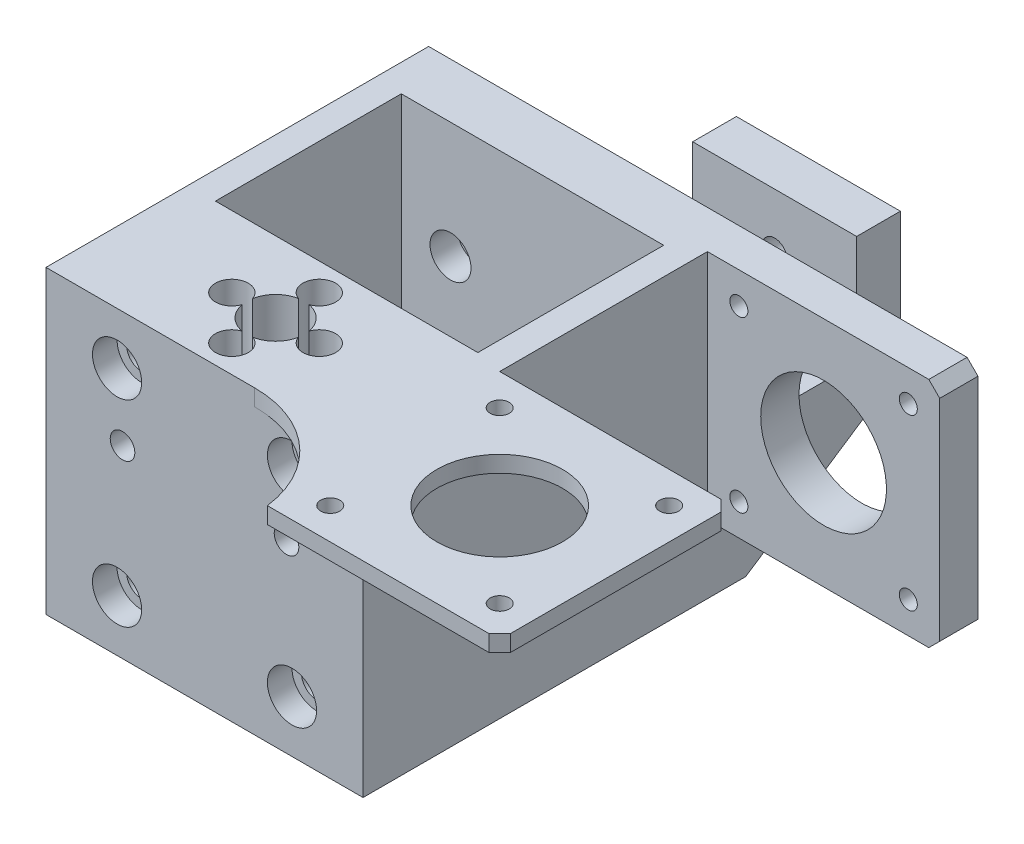
SolidWorks part; units mm, degrees
material "PETG"
ref_plane "Front Plane" through (0, 0, 0) normal (0, 0, 1) x (1, 0, 0)
ref_plane "Top Plane" through (0, 0, 0) normal (0, 1, 0) x (1, 0, 0)
ref_plane "Right Plane" through (0, 0, 0) normal (1, 0, 0) x (0, 0, -1)
sketch "Sketch1" plane through (0, 0, 0) normal (0, 1, 0) x (1, 0, 0)
  line L0 (0, 13) -> (0, -13) construction
  line L1 (-24, -13) -> (24, -13)
  line L3 (-24, 13) -> (24, 13)
  line L5 (-24, -13) -> (24, 13) construction
  line L6 (-24, 13) -> (24, -13) construction
  line L15 (-24, 13) -> (-24, -13) construction
  line L16 (24, -13) -> (24, 13) construction
  line L17 (-24, 13) -> (-24, -13)
  line L18 (24, -13) -> (24, 13)
  circle A0 centre (0, 0) radius 5.25
  point P0 (0, 0)
  dimension "D3" = 10.5
  dimension "D1" = 26
  dimension "D2" = 48
extrude "Boss-Extrude1" add sketch "Sketch1" along normal blind 55
sketch "Sketch2" plane through (0, 0, 13) normal (0, 0, 1) x (1, 0, 0)
  line L0 (0, 55) -> (0, 0) construction
  line L1 (-24, 55) -> (24, 55) construction
  line L2 (-24, 27.5) -> (24, 27.5) construction
  line L7 (-24, 55) -> (-24, 0) construction
  line L8 (24, 55) -> (24, 0) construction
  circle A0 centre (-16, 45.5) radius 2.75
  circle A1 centre (16, 45.5) radius 2.75
  circle A4 centre (16, 9.5) radius 2.75
  circle A5 centre (-16, 9.5) radius 2.75
  dimension "D1" = 5.5
  dimension "D2" = 16
  dimension "D3" = 18
extrude "Cut-Extrude1" cut sketch "Sketch2" against normal up to next
sketch "Sketch3" plane through (0, 0, 13) normal (0, 0, 1) x (1, 0, 0)
  line L0 (0, 55) -> (0, 0) construction
  line L1 (-24, 55) -> (24, 55) construction
  line L2 (-24, 27.5) -> (24, 27.5) construction
  line L7 (-24, 55) -> (-24, 0) construction
  line L8 (24, 55) -> (24, 0) construction
  circle A0 centre (-16, 45.5) radius 4.5
  circle A1 centre (16, 45.5) radius 4.5
  circle A4 centre (16, 9.5) radius 4.5
  circle A5 centre (-16, 9.5) radius 4.5
  dimension "D1" = 9
extrude "Cut-Extrude2" cut sketch "Sketch3" against normal blind 4.5
sketch "Sketch4" plane through (0, 55, 0) normal (0, 1, 0) x (1, 0, 0)
  line L0 (0, 0) -> (0, 13) construction
  line L1 (24, 13) -> (-24, 13) construction
  circle A0 centre (0, 8) radius 1.75
  circle A1 centre (8, 0) radius 1.75
  circle A2 centre (0, -8) radius 1.75
  circle A3 centre (-8, 0) radius 1.75
  point P15 (0, 0)
  dimension "D1" = 3.5
  dimension "D2" = 8
  dimension "D4" = 8
  dimension "D5" = 8
  dimension "D3" = 4
extrude "Cut-Extrude3" cut sketch "Sketch4" against normal up to next
sketch "Sketch5" plane through (0, 55, 0) normal (0, 1, 0) x (1, 0, 0)
  circle A0 centre (0, 8) radius 3
  circle A1 centre (8, 0) radius 3
  circle A2 centre (0, -8) radius 3
  circle A3 centre (-8, 0) radius 3
  circle A4 centre (0, 8) radius 1.75 construction
  point P12 (0, 0)
  dimension "D1" = 6
  dimension "D3" = 8
  dimension "D4" = 8
  dimension "D2" = 4
extrude "Cut-Extrude4" cut sketch "Sketch5" against normal blind 15
sketch "Sketch6" plane through (0, 0, 0) normal (0, -1, 0) x (1, 0, 0)
  circle A0 centre (0, 0) radius 11.25
  dimension "D1" = 22.5
extrude "Cut-Extrude5" cut sketch "Sketch6" against normal blind 30
sketch "Sketch9" plane through (0, 55, 0) normal (0, 1, 0) x (1, 0, 0)
  line L0 (0, -13) -> (0, 13) construction
  line L1 (-24, -13) -> (-29, -13)
  line L2 (-24, -13) -> (-24, 47)
  line L4 (-29, -13) -> (-29, 57)
  line L5 (-24, -13) -> (24, -13) construction
  line L6 (24, 13) -> (-24, 13) construction
  line L8 (29, -13) -> (29, 57)
  line L9 (24, -13) -> (29, -13)
  line L10 (24, -13) -> (24, 47)
  line L12 (24, 47) -> (-24, 47)
  line L14 (29, 57) -> (-29, 57)
  dimension "D1" = 70
  dimension "D2" = 5
  dimension "D3" = 70
  dimension "D4" = 10
extrude "Boss-Extrude3" add sketch "Sketch9" against normal up to surface (55 mm away) up to face at (0, 0, -11.25)
sketch "Sketch10" plane through (0, 0, -57) normal (0, 0, -1) x (-1, 0, 0)
  line L0 (-71.5, 33.75) -> (-29, 33.75) construction
  line L1 (-29, 55) -> (-71.5, 55)
  line L2 (-29, 55) -> (-29, 12.5)
  line L3 (-29, 12.5) -> (-71.5, 12.5)
  line L4 (-71.5, 55) -> (-71.5, 12.5)
  line L5 (-50.25, 55) -> (-50.25, 12.5) construction
  circle A0 centre (-65.75, 49.25) radius 1.65
  circle A1 centre (-34.75, 49.25) radius 1.65
  circle A2 centre (-34.75, 18.25) radius 1.65
  circle A3 centre (-65.75, 18.25) radius 1.65
  circle A4 centre (-50.25, 33.75) radius 11.5
  dimension "D3" = 3.3
  dimension "D4" = 15.5
  dimension "D5" = 15.5
  dimension "D6" = 23
  dimension "D1" = 42.5
  dimension "D2" = 42.5
extrude "Boss-Extrude4" add sketch "Sketch10" against normal blind 7
chamfer "Chamfer1" distance 2 angle 45 2 edges at (71.5, 12.5, -53.5) (71.5, 55, -53.5)
sketch "Sketch11" plane through (0, 55, 0) normal (0, 1, 0) x (1, 0, 0)
  line L0 (29, -13) -> (29, 50) construction
  line L1 (29, 12) -> (71.5, 12)
  line L2 (29, 12) -> (29, -30.5)
  line L3 (29, -30.5) -> (71.5, -30.5)
  line L4 (71.5, 12) -> (71.5, -30.5)
  line L6 (50.25, 12) -> (50.25, -30.5) construction
  line L7 (71.5, -9.25) -> (29, -9.25) construction
  line L8 (29, 50) -> (69.5, 50) construction
  circle A0 centre (50.25, -9.25) radius 11.5
  circle A1 centre (34.75, 6.25) radius 1.75
  circle A2 centre (65.75, 6.25) radius 1.75
  circle A3 centre (65.75, -24.75) radius 1.75
  circle A4 centre (34.75, -24.75) radius 1.75
  dimension "D4" = 23
  dimension "D5" = 3.5
  dimension "D6" = 15.5
  dimension "D7" = 15.5
  dimension "D1" = 42.5
  dimension "D2" = 42.5
  dimension "D3" = 38
extrude "Boss-Extrude5" add sketch "Sketch11" against normal blind 3
fillet "Fillet2" radius 20 1 edges at (29, 53.5, 13)
chamfer "Chamfer2" distance 2 angle 45 2 edges at (71.5, 53.5, -12) (71.5, 53.5, 30.5)
sketch "Sketch12" plane through (29, 0, 0) normal (1, 0, 0) x (0, 0, -1)
  line L0 (57, 0) -> (85.3, 18.75)
  line L1 (12, 55) -> (50, 55) construction
  line L2 (57, 0) -> (57, 12.5) construction
  line L5 (57, 53) -> (57, 14.5) construction
  line L7 (85.3, 18.75) -> (85.3, 23.75)
  line L8 (77.3, 23.75) -> (57, 23.75)
  line L10 (57, 23.75) -> (57, 0)
  line L11 (50, 55) -> (57, 55) construction
  line L13 (85.3, 23.75) -> (85.3, 43.75)
  line L14 (85.3, 43.75) -> (77.3, 43.75)
  line L15 (77.3, 23.75) -> (77.3, 43.75)
  dimension "D1" = 36.25
  dimension "D2" = 28.3
  dimension "D3" = 5
  dimension "D4" = 20
  dimension "D5" = 8
  dimension "D6" = 31.25
extrude "Boss-Extrude6" add sketch "Sketch12" against normal up to surface (58 mm away) up to face at (-29, 27.5, -22)
sketch "Sketch13" plane through (0, 0, -57) normal (0, 0, -1) x (-1, 0, 0)
  line L0 (-29, 23.75) -> (-29, 55) construction
  line L1 (-69.5, 55) -> (29, 55) construction
  line L2 (-29, 33.75) -> (29, 33.75) construction
  line L3 (29, 23.75) -> (29, 55) construction
  line L4 (29, 23.75) -> (29, 55) construction
  line L5 (29, 23.75) -> (-29, 23.75) construction
  circle A1 centre (15, 33.75) radius 2.25
  circle A3 centre (-15, 33.75) radius 2.25
  dimension "D2" = 14
  dimension "D5" = 4.5
  dimension "D6" = 4.5
  dimension "D3" = 14
  dimension "D4" = 30
  dimension "D1" = 10
extrude "Cut-Extrude6" cut sketch "Sketch13" against normal through all contours A3 | A1 region at (-15, 33.75, -57) region at (15, 33.75, -57)
sketch "Sketch14" plane through (0, 0, -47) normal (0, 0, 1) x (1, 0, 0)
  circle A0 centre (-15, 33.75) radius 3.75
  circle A1 centre (15, 33.75) radius 3.75
  circle A3 centre (45, 33.75) radius 3.75 [skipped]
  dimension "D1" = 7.5
  dimension "D3" = 30
  dimension "D2" = 3
extrude "Cut-Extrude7" cut sketch "Sketch14" against normal blind 5
sketch "Sketch15" plane through (0, 0, -85.3) normal (0, 0, -1) x (-1, 0, 0)
  line L0 (-29, 18.75) -> (-29, 43.75) construction
  line L1 (29, 43.75) -> (1, 43.75)
  line L2 (29, 43.75) -> (29, 23.75)
  line L4 (1, 43.75) -> (1, 23.75)
  line L5 (1, 33.75) -> (-29, 33.75) construction
  line L12 (1, 23.75) -> (1, 11.75)
  line L13 (1, 11.75) -> (29, 11.75)
  line L14 (29, 23.75) -> (29, 11.75)
  circle A0 centre (-14, 33.75) radius 2.25
  dimension "D3" = 4.5
  dimension "D1" = 30
  dimension "D2" = 20
  dimension "D4" = 20
  dimension "D5" = 12
extrude "Cut-Extrude8" cut sketch "Sketch15" against normal up to surface (8 mm away) up to face at (0, 33.75, -77.3)
sketch "Sketch16" plane through (0, 0, -85.3) normal (0, 0, -1) x (-1, 0, 0)
  circle A0 centre (-14, 33.75) radius 3.75
  dimension "D1" = 7.5
extrude "Cut-Extrude9" cut sketch "Sketch16" against normal blind 1
sketch "Sketch17" plane through (0, 0, -57) normal (0, 0, -1) x (-1, 0, 0)
  line L0 (-50.25, 33.75) -> (-50.25, 55) construction
  line L1 (-69.5, 55) -> (29, 55) construction
  line L2 (-50.25, 33.75) -> (-71.5, 33.75) construction
  line L3 (-71.5, 53) -> (-71.5, 14.5) construction
  circle A0 centre (-65.75, 49.25) radius 3
  circle A1 centre (-34.75, 49.25) radius 3
  circle A2 centre (-34.75, 18.25) radius 3
  circle A3 centre (-65.75, 18.25) radius 3
  dimension "D1" = 6
extrude "Cut-Extrude10" cut sketch "Sketch17" against normal blind 2
